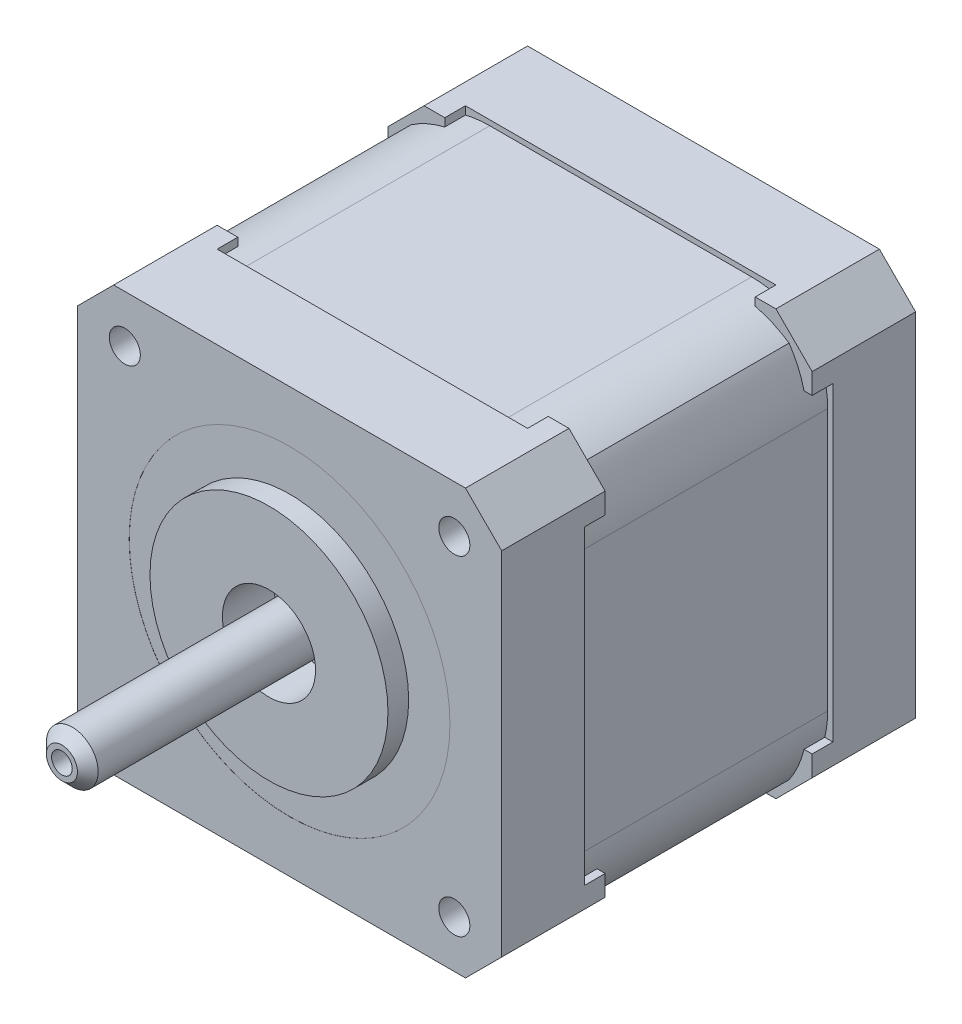
SolidWorks part; units mm, degrees
ref_plane "Ön Düzlem" through (0, 0, 0) normal (0, 0, 1) x (1, 0, 0)
ref_plane "Üst Düzlem" through (0, 0, 0) normal (0, 1, 0) x (1, 0, 0)
ref_plane "Sağ Düzlem" through (0, 0, 0) normal (1, 0, 0) x (0, 0, -1)
sketch "Çizim1" plane through (0, 0, 0) normal (0, 0, 1) x (1, 0, 0)
  line L3 (-17, 41) -> (17, 41)
  line L4 (20.5, 3.5) -> (20.5, 37.5)
  line L5 (-20.5, 3.5) -> (-20.5, 37.5)
  line L6 (17, 41) -> (20.5, 37.5)
  line L7 (-17, 41) -> (-20.5, 37.5)
  line L8 (17, 0) -> (20.5, 3.5)
  line L9 (-17, 0) -> (-20.5, 3.5)
  line L10 (-17, 0) -> (17, 0)
extrude "Yükseklik-Ekstrüzyon2" add sketch "Çizim1" along normal blind 8
sketch "Çizim5" plane through (0, 0, 0) normal (0, 0, -1) x (-1, 0, 0)
  line L0 (-20.5, 3.5) -> (-20.5, 5.5)
  line L1 (-20.5, 3.5) -> (-20.5, 37.5) construction
  line L2 (-20.5, 5.5) -> (-20, 5.5)
  line L3 (-17, 0) -> (-15, 0)
  line L4 (17, 0) -> (-17, 0) construction
  line L5 (-15, 0) -> (-15, 0.5)
  line L6 (20.5, 20.5) -> (10.3627, 20.5)
  line L7 (15, 0) -> (15, 0.5)
  line L8 (-20, 3.7071) -> (-20, 37.2929)
  line L9 (-20, 37.2929) -> (-16.7929, 40.5)
  line L10 (-16.7929, 40.5) -> (16.7929, 40.5)
  line L11 (16.7929, 40.5) -> (20, 37.2929)
  line L12 (20, 37.2929) -> (20, 3.7071)
  line L13 (20, 3.7071) -> (16.7929, 0.5)
  line L14 (16.7929, 0.5) -> (-16.7929, 0.5)
  line L15 (-16.7929, 0.5) -> (-20, 3.7071)
  line L16 (17, 0) -> (15, 0)
  line L17 (20.5, 5.5) -> (20, 5.5)
  line L18 (20.5, 3.5) -> (20.5, 5.5)
  line L19 (20.5, 37.5) -> (20.5, 3.5) construction
  line L20 (-20.5, 35.5) -> (-20, 35.5)
  line L21 (-15, 41) -> (-15, 40.5)
  line L22 (15, 41) -> (15, 40.5)
  line L23 (20.5, 37.5) -> (20.5, 35.5)
  line L24 (20.5, 35.5) -> (20, 35.5)
  line M4 (20.5, 37.5) -> (17, 41)
  line M5 (17, 41) -> (-17, 41)
  line M6 (-17, 41) -> (-20.5, 37.5)
  line M7 (-20.5, 37.5) -> (-20.5, 3.5)
  line M8 (-20.5, 3.5) -> (-17, 0)
  line M9 (-17, 0) -> (17, 0)
  line M10 (17, 0) -> (20.5, 3.5)
  line M11 (20.5, 3.5) -> (20.5, 37.5)
extrude "Yükseklik-Ekstrüzyon10" add sketch "Çizim5" along normal blind 2 contours L21 L20 L8 L9 L10 M5 M6 M7 | L24 L22 L10 L11 L12 M11 M4 M5 | L17 L12 L13 L14 L7 M11 M9 M10 | L14 L15 L8 L2 L5 M7 M8 M9
sketch "Çizim12" plane through (0, 0, 0) normal (0, 0, -1) x (-1, 0, 0)
  line L1 (-20.5, 5.5) -> (-20.5, 3.5)
  line L2 (-20.5, 3.5) -> (-17, 0)
  line L3 (-17, 0) -> (17, 0)
  line L4 (17, 0) -> (20.5, 3.5)
  line L5 (20.5, 3.5) -> (20.5, 37.5)
  line L6 (20.5, 37.5) -> (17, 41)
  line L7 (17, 41) -> (-17, 41)
  line L8 (-17, 41) -> (-20.5, 37.5)
  line L9 (-20.5, 37.5) -> (-20.5, 35.5)
  line L10 (-20.5, 35.5) -> (-20.4853, 35.5072)
  line L11 (-20, 35.5) -> (-20, 5.5)
  line L12 (-20, 5.5) -> (-20, 3.7071)
  line L13 (-20, 3.7071) -> (-16.7929, 0.5)
  line L14 (-16.7929, 0.5) -> (16.7929, 0.5)
  line L15 (16.7929, 0.5) -> (20, 3.7071)
  line L16 (20, 3.7071) -> (20, 37.2929)
  line L17 (20, 37.2929) -> (16.7929, 40.5)
  line L18 (16.7929, 40.5) -> (-16.7929, 40.5)
  line L19 (-16.7929, 40.5) -> (-20, 37.2929)
  line L20 (-20, 37.2929) -> (-20, 35.5)
  line L21 (-20.5, 35.5) -> (-20.5, 5.5) construction
  line M3 (-20, 5.5) -> (-20, 3.7071)
  line M4 (-20, 3.7071) -> (-16.7929, 0.5)
  line M5 (-16.7929, 0.5) -> (-15, 0.5)
  line M9 (15, 0.5) -> (16.7929, 0.5)
  line M10 (16.7929, 0.5) -> (20, 3.7071)
  line M11 (20, 3.7071) -> (20, 5.5)
  line M15 (20, 35.5) -> (20, 37.2929)
  line M16 (20, 37.2929) -> (16.7929, 40.5)
  line M17 (16.7929, 40.5) -> (15, 40.5)
  line M21 (-15, 40.5) -> (-16.7929, 40.5)
  line M22 (-16.7929, 40.5) -> (-20, 37.2929)
  line M23 (-20, 37.2929) -> (-20, 35.5)
  dimension "D1" = 0.5
extrude "Yükseklik-Ekstrüzyon11" add sketch "Çizim12" along normal blind 24 contours L18 L11 L14 L16 M17 M21 M22 M23 M3 M4 M5 M9 M10 M11 M15 M16
sketch "Çizim13" plane through (0, 0, -24) normal (0, 0, -1) x (-1, 0, 0)
  line L0 (-17, 41) -> (-20.5, 37.5)
  line L1 (-20.5, 37.5) -> (-20.5, 3.5)
  line L2 (-20.5, 3.5) -> (-17, 0)
  line L3 (-17, 0) -> (17, 0)
  line L4 (17, 0) -> (20.5, 3.5)
  line L5 (20.5, 3.5) -> (20.5, 37.5)
  line L6 (20.5, 37.5) -> (17, 41)
  line L7 (17, 41) -> (-17, 41)
extrude "Yükseklik-Ekstrüzyon12" add sketch "Çizim13" along normal blind 8
sketch "Çizim14" plane through (0, 0, -24) normal (0, 0, 1) x (1, 0, 0)
  line L0 (17, 41) -> (15, 41)
  line L1 (-17, 41) -> (17, 41) construction
  line L2 (15, 41) -> (15, 40.5)
  line L3 (-16.7929, 40.5) -> (16.7929, 40.5) construction
  line L4 (15, 40.5) -> (16.7929, 40.5)
  line L5 (16.7929, 40.5) -> (20, 37.2929)
  line L6 (20.5, 37.5) -> (20.5, 35.5)
  line L7 (20.5, 37.5) -> (20.5, 3.5) construction
  line L8 (20.5, 35.5) -> (20, 35.5)
  line L9 (20, 37.2929) -> (20, 3.7071) construction
  line L10 (20, 35.5) -> (20, 37.2929)
  line L11 (20.5, 37.5) -> (17, 41)
  line L12 (0, 0) -> (0, 15.5815)
  line L13 (17, 0) -> (15, 0)
  line L14 (15, 0) -> (15, 0.5)
  line L15 (15, 0.5) -> (16.7929, 0.5)
  line L16 (20.5, 3.5) -> (17, 0)
  line L17 (16.7929, 0.5) -> (20, 3.7071)
  line L18 (20, 5.5) -> (20, 3.7071)
  line L19 (20.5, 3.5) -> (20.5, 5.5)
  line L20 (20.5, 5.5) -> (20, 5.5)
  line L21 (-20.5, 5.5) -> (-20, 5.5)
  line L22 (-20.5, 3.5) -> (-20.5, 5.5)
  line L23 (-20, 5.5) -> (-20, 3.7071)
  line L24 (-20.5, 3.5) -> (-17, 0)
  line L25 (-16.7929, 0.5) -> (-20, 3.7071)
  line L26 (-15, 0.5) -> (-16.7929, 0.5)
  line L27 (-15, 0) -> (-15, 0.5)
  line L28 (-17, 0) -> (-15, 0)
  line L29 (-20.5, 35.5) -> (-20, 35.5)
  line L30 (-20, 35.5) -> (-20, 37.2929)
  line L31 (-20.5, 37.5) -> (-20.5, 35.5)
  line L32 (-20.5, 37.5) -> (-17, 41)
  line L33 (-16.7929, 40.5) -> (-20, 37.2929)
  line L34 (-15, 40.5) -> (-16.7929, 40.5)
  line L35 (-17, 41) -> (-15, 41)
  line L36 (-15, 41) -> (-15, 40.5)
  line M19 (17, 41) -> (-17, 41)
  line M20 (-17, 41) -> (-20.5, 37.5)
  line M21 (-20.5, 37.5) -> (-20.5, 3.5)
  line M22 (-20.5, 3.5) -> (-17, 0)
  line M23 (-17, 0) -> (17, 0)
  line M24 (17, 0) -> (20.5, 3.5)
  line M25 (20.5, 3.5) -> (20.5, 37.5)
  line M26 (20.5, 37.5) -> (17, 41)
  line M27 (20, 37.2929) -> (20, 3.7071)
  line M28 (20, 3.7071) -> (16.7929, 0.5)
  line M29 (16.7929, 0.5) -> (-16.7929, 0.5)
  line M30 (-16.7929, 0.5) -> (-20, 3.7071)
  line M31 (-20, 3.7071) -> (-20, 37.2929)
  line M32 (-20, 37.2929) -> (-16.7929, 40.5)
  line M33 (-16.7929, 40.5) -> (16.7929, 40.5)
  line M34 (16.7929, 40.5) -> (20, 37.2929)
extrude "Yükseklik-Ekstrüzyon14" add sketch "Çizim14" along normal blind 2 contours L36 L29 M19 M20 M21 M31 M32 M33 | L27 L21 M23 M29 M30 M31 M21 M22 | L20 L14 M25 M27 M28 M29 M23 M24 | L8 L2 M25 M26 M19 M33 M34 M27
fillet "Radyus5" radius 10 8 edges at (-16.7929, 0.5, -12) (-20, 3.7071, -12) (-20, 37.2929, -12) (-16.7929, 40.5, -12) (20, 37.2929, -12) (16.7929, 40.5, -12) (20, 3.7071, -12) (16.7929, 0.5, -12)
sketch "Çizim15" plane through (0, 0, -32) normal (0, 0, -1) x (-1, 0, 0)
  circle A0 centre (0, 20.5) radius 4.5
extrude "Kes-Ekstrüzyon3" cut sketch "Çizim15" against normal blind 3
fillet "Radyus6" radius 0.5 1 edges at (-4.5, 20.5, -32)
sketch "Çizim16" plane through (0, 0, -29) normal (0, 0, -1) x (-1, 0, 0)
  circle A0 centre (0, 20.5) radius 3
extrude "Yükseklik-Ekstrüzyon15" add sketch "Çizim16" along normal blind 1
fillet "Radyus7" radius 0.5 1 edges at (-3, 20.5, -30)
sketch "Çizim17" plane through (0, 0, -30) normal (0, 0, -1) x (-1, 0, 0)
  line L1 (1.2603, 19.7965) -> (1.2394, 21.2397)
  line L2 (1.2394, 21.2397) -> (-0.0209, 21.9432)
  line L3 (-0.0209, 21.9432) -> (-1.2603, 21.2035)
  line L4 (-1.2603, 21.2035) -> (-1.2394, 19.7603)
  line L5 (-1.2394, 19.7603) -> (0.0209, 19.0568)
  line L6 (0.0209, 19.0568) -> (1.2603, 19.7965)
  circle A0 centre (0, 20.5) radius 1.25 construction
extrude "Kes-Ekstrüzyon4" cut sketch "Çizim17" against normal blind 0.5
sketch "Çizim18" plane through (0, 0, -32) normal (0, 0, -1) x (-1, 0, 0)
  line L0 (0, 20.5) -> (0, 35.5)
  line L1 (0, 20.5) -> (15, 20.5)
  line L2 (0, 35.5) -> (15, 35.5)
  line L3 (15, 35.5) -> (15, 20.5)
  circle A0 centre (15, 35.5) radius 3
  circle A1 centre (15, 5.5) radius 3
  circle A2 centre (-15, 5.5) radius 3
  circle A3 centre (-15, 35.5) radius 3
extrude "Kes-Ekstrüzyon5" cut sketch "Çizim18" against normal blind 1 contours A2 | A0 | A1 | A3
sketch "Çizim19" plane through (0, 0, -31) normal (0, 0, -1) x (-1, 0, 0)
  circle A0 centre (15, 35.5) radius 2
  circle A1 centre (15, 5.5) radius 2
  circle A2 centre (-15, 5.5) radius 2
  circle A3 centre (-15, 35.5) radius 2
extrude "Yükseklik-Ekstrüzyon17" add sketch "Çizim19" along normal blind 0.5
fillet "Radyus8" radius 0.5 4 edges at (13, 5.5, -31.5) (-13, 5.5, -31.5) (-17, 35.5, -31.5) (17, 35.5, -31.5)
sketch "Çizim21" plane through (0, 0, -31.5) normal (0, 0, -1) x (-1, 0, 0)
  line L0 (0, 20.5) -> (9.2525, 20.5)
  line L1 (9.2525, 20.5) -> (0, 20.5)
  line L2 (0, 20.5) -> (0, 30.2455)
  line L3 (15.15, 6.5) -> (14.85, 6.5)
  line L4 (15.15, 35.65) -> (15.15, 36.5)
  line L5 (15.15, 35.35) -> (16, 35.35)
  line L6 (14.85, 35.35) -> (14.85, 34.5)
  line L7 (14.85, 35.65) -> (14, 35.65)
  line L8 (14.85, 35.65) -> (14.85, 36.5)
  line L9 (15.15, 35.65) -> (16, 35.65)
  line L10 (15.15, 35.35) -> (15.15, 34.5)
  line L11 (14.85, 35.35) -> (14, 35.35)
  line L12 (14.85, 36.5) -> (15.15, 36.5)
  line L13 (16, 35.65) -> (16, 35.35)
  line L14 (15.15, 34.5) -> (14.85, 34.5)
  line L15 (14, 35.35) -> (14, 35.65)
  line L16 (14, 35.65) -> (14.0342, 35.6422)
  line L17 (14, 5.35) -> (14.0342, 5.3578)
  line L18 (14, 5.65) -> (14, 5.35)
  line L19 (16, 5.35) -> (16, 5.65)
  line L20 (14.85, 5.65) -> (14, 5.65)
  line L21 (15.15, 5.65) -> (15.15, 6.5)
  line L22 (15.15, 5.35) -> (16, 5.35)
  line L23 (14.85, 5.35) -> (14, 5.35)
  line L24 (14.85, 5.65) -> (14.85, 6.5)
  line L25 (15.15, 5.65) -> (16, 5.65)
  line L26 (14.85, 4.5) -> (15.15, 4.5)
  line L27 (14.85, 5.35) -> (14.85, 4.5)
  line L28 (15.15, 5.35) -> (15.15, 4.5)
  line L29 (-14, 35.65) -> (-14.0342, 35.6422)
  line L30 (-14, 35.35) -> (-14, 35.65)
  line L31 (-14.85, 36.5) -> (-15.15, 36.5)
  line L32 (-15.15, 34.5) -> (-14.85, 34.5)
  line L33 (-16, 35.65) -> (-16, 35.35)
  line L34 (-14.85, 35.35) -> (-14, 35.35)
  line L35 (-15.15, 35.35) -> (-15.15, 34.5)
  line L36 (-15.15, 35.65) -> (-16, 35.65)
  line L37 (-14.85, 35.65) -> (-14.85, 36.5)
  line L38 (-14.85, 35.65) -> (-14, 35.65)
  line L39 (-14.85, 35.35) -> (-14.85, 34.5)
  line L40 (-15.15, 35.35) -> (-16, 35.35)
  line L41 (-15.15, 35.65) -> (-15.15, 36.5)
  line L42 (-16, 5.35) -> (-16, 5.65)
  line L43 (-15.15, 5.35) -> (-15.15, 4.5)
  line L44 (-14.85, 5.35) -> (-14.85, 4.5)
  line L45 (-14.85, 4.5) -> (-15.15, 4.5)
  line L46 (-15.15, 5.65) -> (-16, 5.65)
  line L47 (-14.85, 5.65) -> (-14.85, 6.5)
  line L48 (-14.85, 5.35) -> (-14, 5.35)
  line L49 (-15.15, 5.35) -> (-16, 5.35)
  line L50 (-15.15, 5.65) -> (-15.15, 6.5)
  line L51 (-14.85, 5.65) -> (-14, 5.65)
  line L52 (-14, 5.65) -> (-14, 5.35)
  line L53 (-14, 5.35) -> (-14.0342, 5.3578)
  line L54 (-15.15, 6.5) -> (-14.85, 6.5)
  point P0 (15, 35.5)
  point P1 (15, 36.5)
  point P3 (15.15, 35.5)
  point P4 (16, 35.5)
  point P5 (15, 34.5)
  point P10 (14.85, 35.5)
  point P14 (14.85, 35.5)
extrude "Kes-Ekstrüzyon6" cut sketch "Çizim21" against normal blind 0.1
sketch "Çizim22" plane through (0, 0, 8) normal (0, 0, 1) x (1, 0, 0)
  circle A0 centre (0, 20.5) radius 4.5
extrude "Kes-Ekstrüzyon7" cut sketch "Çizim22" against normal blind 3
sketch "Çizim23" plane through (0, 0, 5) normal (0, 0, 1) x (1, 0, 0)
  circle A0 centre (0, 20.5) radius 2.5
extrude "Yükseklik-Ekstrüzyon18" add sketch "Çizim23" along normal blind 25
sketch "Çizim24" plane through (0, 0, 30) normal (0, 0, 1) x (1, 0, 0)
  circle A0 centre (0, 20.5) radius 1
extrude "Kes-Ekstrüzyon8" cut sketch "Çizim24" against normal blind 2
chamfer "Pah1" distance 1 angle 45 1 edges at (2.5, 20.5, 30)
sketch "Çizim25" plane through (0, 0, 8) normal (0, 0, 1) x (1, 0, 0)
  line L0 (20.5, 20.5) -> (15.5, 20.5)
  line L1 (20.5, 3.5) -> (20.5, 37.5) construction
  circle A0 centre (0, 20.5) radius 4.5
  circle A1 centre (0, 20.5) radius 15.5
  circle M2 centre (0, 20.5) radius 4.5
extrude "Kes-Ekstrüzyon9" cut sketch "Çizim25" against normal blind 0.01 contours A1 M2
sketch "Çizim26" plane through (0, 0, 7.99) normal (0, 0, 1) x (1, 0, 0)
  line L0 (15.5, 20.5) -> (11.5, 20.5)
  circle A0 centre (0, 20.5) radius 4.5
  circle A1 centre (0, 20.5) radius 15.5 construction
  circle A2 centre (0, 20.5) radius 11.5
  circle M2 centre (0, 20.5) radius 4.5
extrude "Yükseklik-Ekstrüzyon19" add sketch "Çizim26" along normal blind 2 contours A2 M2
sketch "Çizim28" plane through (0, 0, 8) normal (0, 0, 1) x (1, 0, 0)
  line L2 (0, 20.5) -> (0, 27.7903)
  line L3 (0, 27.7903) -> (0, 20.5)
  line L4 (0, 20.5) -> (6.5303, 20.5)
  circle A0 centre (-15.9216, 36.4216) radius 1.5
  circle A1 centre (15.9216, 36.4216) radius 1.5
  circle A2 centre (-15.9216, 4.5784) radius 1.5
  circle A3 centre (15.9216, 4.5784) radius 1.5
extrude "Kes-Ekstrüzyon10" cut sketch "Çizim28" against normal blind 6 contours A1 | A0 | A3 | A2
